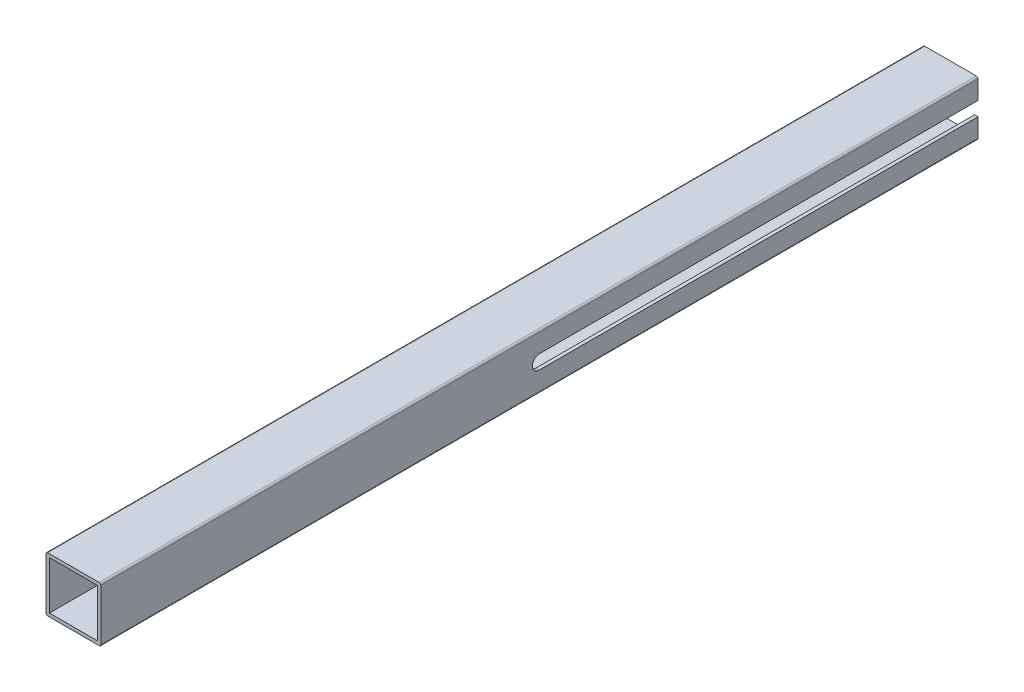
SolidWorks part; units mm, degrees
ref_plane "Front Plane" through (0, 0, 0) normal (0, 0, 1) x (1, 0, 0)
ref_plane "Top Plane" through (0, 0, 0) normal (0, 1, 0) x (1, 0, 0)
ref_plane "Right Plane" through (0, 0, 0) normal (1, 0, 0) x (0, 0, -1)
sketch "Sketch1" plane through (0, 0, 0) normal (0, 0, 1) x (1, 0, 0)
  line L0 (-11.1125, -11.1125) -> (-11.1125, 11.1125)
  line L1 (-12.7, -12.7) -> (12.7, -12.7)
  line L2 (-12.7, -12.7) -> (-12.7, 12.7)
  line L3 (-12.7, 12.7) -> (12.7, 12.7)
  line L4 (12.7, -12.7) -> (12.7, 12.7)
  line L5 (-12.7, -12.7) -> (12.7, 12.7) construction
  line L6 (-12.7, 12.7) -> (12.7, -12.7) construction
  line L7 (-11.1125, 11.1125) -> (11.1125, 11.1125)
  line L8 (11.1125, -11.1125) -> (11.1125, 11.1125)
  line L9 (-11.1125, -11.1125) -> (11.1125, -11.1125)
  point P0 (0, 0)
  point P10 (-11.1125, -12.7)
  dimension "Outside Width" = 25.4
  dimension "Outside Height" = 25.4
  dimension "Wall Thickness" = 1.5875
sketch "Sketch2" plane through (0, 0, 0) normal (1, 0, 0) x (0, 0, -1)
  line L0 (-203.2, 12.7) -> (203.2, 12.7) construction
  point P2 (0, 12.7)
  point P3 (-177.8, 12.7)
  point P5 (177.8, 12.7)
  dimension "Length" = 406.4
  dimension "D2" = 25.4
extrude "Boss-Extrude1" add sketch "Sketch1" along normal up to vertex (203.2 mm away) and the other way up to vertex (203.2 mm away) up to point (0, 12.7, 203.2) other way up to point (0, 12.7, -203.2)
fillet "Fillet1" radius 0.7937 4 edges at (12.7, 12.7, 0) (-12.7, 12.7, 0) (-12.7, -12.7, 0) (12.7, -12.7, 0)
ref_axis "Center Axis 1" through (0, 0, -1005.84) along (0, 0, 1)
sketch "Sketch3" plane through (12.7, 0, 0) normal (1, 0, 0) x (0, 0, -1)
  line L0 (0, 0) -> (203.2, 0) construction
  line L1 (203.2, -11.9062) -> (203.2, 11.9063) construction
  line L2 (0, 3.2639) -> (203.2, 3.2639)
  line L3 (0, -3.2639) -> (203.2, -3.2639)
  arc A0 (0, 3.2639) -> (0, -3.2639) centre (0, 0) ccw
  arc A1 (203.2, -3.2639) -> (203.2, 3.2639) centre (203.2, 0) ccw
  point P5 (101.6, 0)
  dimension "D1" = 6.5278
extrude "Cut-Extrude1" cut sketch "Sketch3" against normal through all
equation "\"D1@Fillet1\"=\"Wall Thickness@Sketch1\"/2"
equation "\"D1@Sketch2\"=\"Outside Width@Sketch1\""
equation "\"D2@Sketch2\"=\"D1@Sketch2\""
